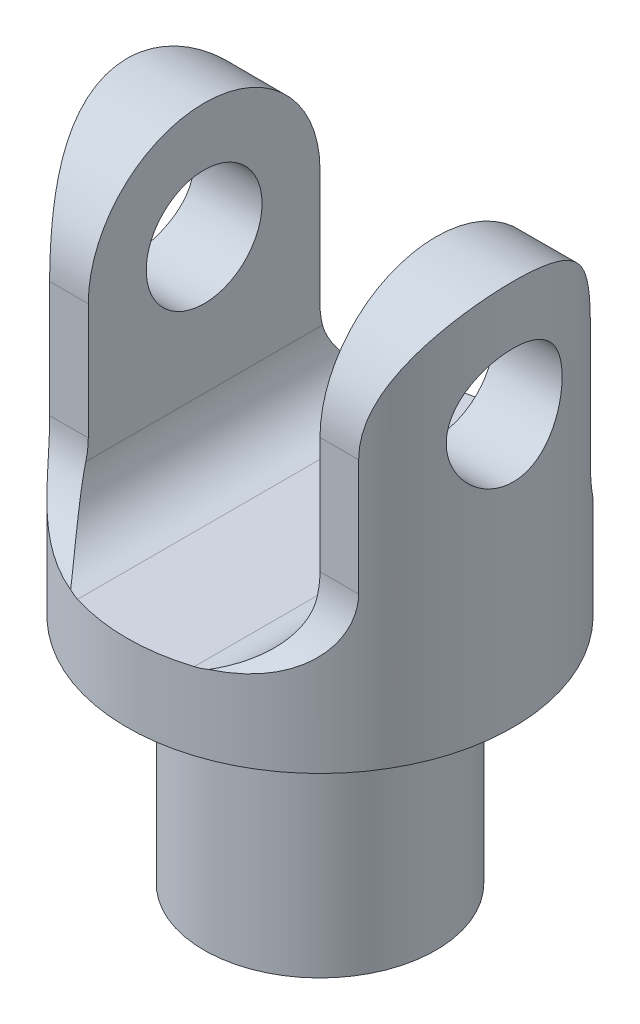
SolidWorks part; units mm, degrees
ref_plane "Alzado" through (0, 0, 0) normal (0, 0, 1) x (1, 0, 0)
ref_plane "Planta" through (0, 0, 0) normal (0, 1, 0) x (1, 0, 0)
ref_plane "Vista lateral" through (0, 0, 0) normal (1, 0, 0) x (0, 0, -1)
sketch "Croquis1" plane through (0, 0, 0) normal (0, 0, 1) x (1, 0, 0)
  line L0 (3, 5) -> (5, 5)
  line L1 (-5, -5) -> (5, -5) construction
  line L2 (-5, -5) -> (-5, 5) construction
  line L3 (-5, 5) -> (5, 5) construction
  line L4 (5, -5) -> (5, 5) construction
  line L5 (-5, -5) -> (5, 5) construction
  line L6 (-5, 5) -> (5, -5) construction
  line L7 (5, 5) -> (5, -5)
  line L8 (5, -5) -> (3, -5)
  line L9 (3, -5) -> (3, -11)
  line L10 (3, -11) -> (0, -11)
  line L11 (0, -3) -> (0, 5)
  line L12 (0, 5) -> (3, 5)
  line L13 (0, -3) -> (0, -11)
  point P0 (0, 0)
  dimension "D1" = 10
  dimension "D2" = 10
  dimension "D3" = 3
  dimension "D4" = 10
  dimension "D5" = 6
  dimension "D6" = 2
  dimension "D7" = 2
revolve "Revolución1" add sketch "Croquis1" angle 360 about L13
sketch "Croquis2" plane through (0, 0, 0) normal (1, 0, 0) x (0, 0, -1)
  line L0 (0, 5) -> (0, 3.5) construction
  line L1 (5, 5) -> (-5, 5) construction
  line L2 (0, 3.5) -> (0, 2) construction
  line L3 (-5, -3) -> (-4.99, -3)
  line L4 (-3, -1.01) -> (-3, 2)
  line L6 (5, -5) -> (5, 5) construction
  line L7 (3, 2) -> (3, -1.01)
  line L8 (4.99, -3) -> (5, -3)
  line L9 (-5, -5) -> (5, -5) construction
  line L10 (-5, 5) -> (-5, -5) construction
  line L11 (-5, 5) -> (0, 5)
  line L12 (0, 5) -> (5, 5)
  line L14 (5, 5) -> (5, -3)
  line L15 (-5, 5) -> (-5, -3)
  circle A0 centre (0, 2) radius 1.5
  arc A1 (-3, 2) -> (0, 5) centre (0, 2) cw
  arc A2 (3, -1.01) -> (4.99, -3) centre (4.99, -1.01) ccw
  arc A3 (-4.99, -3) -> (-3, -1.01) centre (-4.99, -1.01) ccw
  arc A4 (3, 2) -> (0, 5) centre (0, 2) ccw
  dimension "D3" = 2
  dimension "D5" = 1.99
  dimension "D1" = 1.5
  dimension "D2" = 1.5
  dimension "D4" = 2
  dimension "D6" = 6
extrude "Cortar-Extruir1" cut sketch "Croquis2" against normal blind 5 and the other way blind 5 contours A3 A1 L11 | A4 A2 L12 | A0 region at (0, 1.5534, 3.8388) region at (0, 1.5534, -3.8388) region at (0, 2, 0)
sketch "Croquis3" plane through (0, 0, 0) normal (0, 0, 1) x (1, 0, 0)
  line L0 (3, -1.51) -> (3, 5)
  line L1 (1.51, -3) -> (-1.51, -3)
  line L2 (3, 5) -> (-3, 5)
  line L3 (-3, -1.51) -> (-3, 5)
  arc A0 (3, -1.51) -> (1.51, -3) centre (1.51, -1.51) cw
  arc A1 (-1.51, -3) -> (-3, -1.51) centre (-1.51, -1.51) cw
  dimension "D1" = 1.49
extrude "Cortar-Extruir2" cut sketch "Croquis3" against normal blind 5 and the other way blind 5
